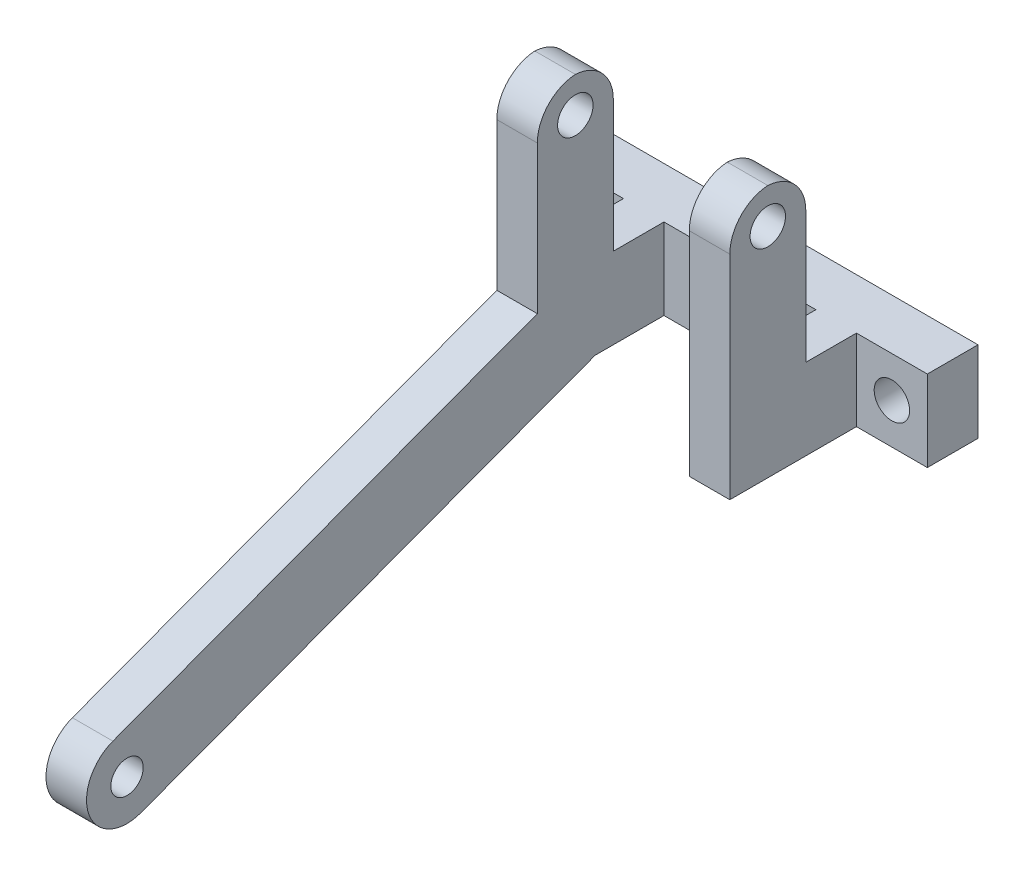
SolidWorks part; units mm, degrees
ref_plane "Front Plane" through (0, 0, 0) normal (0, 0, 1) x (1, 0, 0)
ref_plane "Top Plane" through (0, 0, 0) normal (0, 1, 0) x (1, 0, 0)
ref_plane "Right Plane" through (0, 0, 0) normal (1, 0, 0) x (0, 0, -1)
sketch "Sketch1" plane through (0, 0, 0) normal (0, 0, 1) x (1, 0, 0)
  line L0 (15, 0) -> (-15, 0) construction
  line L1 (-18.5, 4) -> (18.5, 4)
  line L2 (-18.5, 4) -> (-18.5, -4)
  line L3 (-18.5, -4) -> (18.5, -4)
  line L4 (18.5, 4) -> (18.5, -4)
  line L5 (-18.5, 4) -> (18.5, -4) construction
  line L6 (-18.5, -4) -> (18.5, 4) construction
  line L7 (0, -4) -> (0, 4) construction
  circle A0 centre (-15, 0) radius 1.75
  circle A1 centre (15, 0) radius 1.75
  point P0 (0, 0)
  point P12 (0, 0)
  dimension "D3" = 3.5
  dimension "D1" = 37
  dimension "D2" = 8
  dimension "D4" = 15
extrude "Boss-Extrude1" add sketch "Sketch1" along normal blind 5
sketch "Sketch2" plane through (0, 0, 5) normal (0, 0, 1) x (1, 0, 0)
  line L0 (0, 4) -> (0, -4) construction
  line L1 (18.5, 4) -> (-18.5, 4) construction
  line L2 (-18.5, -4) -> (18.5, -4) construction
  line L3 (11.5, -4) -> (7.5, 4) construction
  line L4 (-11.5, 4) -> (-7.5, 4)
  line L5 (-11.5, 4) -> (-11.5, -4)
  line L6 (-11.5, -4) -> (-7.5, -4)
  line L7 (-7.5, 4) -> (-7.5, -4)
  line L8 (-11.5, 4) -> (-7.5, -4) construction
  line L9 (-11.5, -4) -> (-7.5, 4) construction
  line L10 (11.5, 4) -> (7.5, -4) construction
  line L11 (7.5, 4) -> (7.5, -4)
  line L12 (11.5, -4) -> (7.5, -4)
  line L13 (11.5, 4) -> (11.5, -4)
  line L14 (11.5, 4) -> (7.5, 4)
  point P6 (-9.5, 0)
  point P15 (9.5, 0)
  dimension "D1" = 7.5
  dimension "D2" = 4
extrude "Boss-Extrude2" add sketch "Sketch2" along normal blind 12.5
sketch "Sketch4" plane through (0, 4, 0) normal (0, 1, 0) x (1, 0, 0)
  line L0 (-7.5, -17.5) -> (-7.5, -5) construction
  line L1 (-11.5, -17.5) -> (-7.5, -17.5)
  line L2 (-11.5, -17.5) -> (-11.5, -10)
  line L3 (-11.5, -10) -> (-7.5, -10)
  line L4 (-7.5, -17.5) -> (-7.5, -10)
  line L5 (0, 0) -> (0, -5) construction
  line L6 (7.5, -5) -> (-7.5, -5) construction
  line L7 (7.5, -17.5) -> (7.5, -10)
  line L8 (11.5, -10) -> (7.5, -10)
  line L9 (11.5, -17.5) -> (11.5, -10)
  line L10 (11.5, -17.5) -> (7.5, -17.5)
  dimension "D1" = 7.5
extrude "Boss-Extrude3" add sketch "Sketch4" along normal blind 17
sketch "Sketch3" plane through (-11.5, 0, 0) normal (-1, 0, 0) x (0, 0, 1)
  line L0 (10, 17.5) -> (17.5, 17.5) construction
  line L4 (10, 21) -> (10, 4) construction
  line L5 (17.5, 21) -> (17.5, -4) construction
  line L6 (13.75, 17.5) -> (13.75, 21) construction
  line L7 (10, 21) -> (17.5, 21) construction
  circle A0 centre (13.75, 17.5) radius 1.75
  dimension "D1" = 3.5
  dimension "D2" = 17.5
extrude "Cut-Extrude1" cut sketch "Sketch3" against normal through all
fillet "Fillet1" radius 4 4 edges at (-9.5, 21, 10) (9.5, 21, 10) (9.5, 21, 17.5) (-9.5, 21, 17.5)
sketch "Sketch5" plane through (-7.5, 0, 0) normal (1, 0, 0) x (0, 0, -1)
  line L0 (-10, 17) -> (-10, 4) construction
  line L1 (-10, 6.5) -> (-13, 6.5)
  line L2 (-10, 6.5) -> (-10, 1.5)
  line L3 (-10, 1.5) -> (-13, 1.5)
  line L4 (-13, 6.5) -> (-13, 1.5)
  line L5 (-10, 4) -> (-5, 4) construction
  dimension "D1" = 3
  dimension "D2" = 5
  dimension "D3" = 2.5
extrude "Boss-Extrude4" [suppressed] add sketch "Sketch5" along normal up to next
sketch "Sketch6" plane through (-11.5, 0, 0) normal (-1, 0, 0) x (0, 0, 1)
  line L0 (56.6083, -20.6814) -> (11.7824, -4)
  line L1 (17.5, -4) -> (5, -4) construction
  line L2 (11.7824, -4) -> (17.5, 2.4083)
  line L3 (13.75, 17.5) -> (58.0033, -16.9326) construction
  line L4 (17.5, 2.4083) -> (59.3984, -13.1837)
  line L5 (59.3984, -13.1837) -> (56.6083, -20.6814) construction
  line L6 (13.75, 17.5) -> (13.75, -4) construction
  line L7 (17.5, 17) -> (17.5, -4) construction
  circle A0 centre (58.0033, -16.9326) radius 1.6
  arc A1 (56.6083, -20.6814) -> (59.3984, -13.1837) centre (58.0033, -16.9326) ccw
  dimension "D1" = 3.2
  dimension "D2" = 8
  dimension "D3" = 52.114
  dimension "D4" = 56.071
  dimension "D5" = 1.9676
extrude "Boss-Extrude5" add sketch "Sketch6" against normal up to surface (4 mm away) up to face at (-7.5, 15.75, 13.75)
equation "\"X-ROD-SPACING\"=45"
equation "\"Y-ROD-SPACING\"=75"
equation "\"Z-ROD-SPACING\"=17.5"
equation "\"Y-BED-OFFSET\"=2"
equation "\"Y-BED-ROD-INSET\"=3.5"
equation "\"Y-BED-SCREW-SPACING\"=209"
equation "\"Y-BED-SCREW-CUTOUT-SLOT-HEIGHT\"=2"
equation "\"T-SLOT-NUT-FILLET-RADIUS\"=0.25"
equation "\"T-SLOT-SCREW-SHAFT-RADIUS\"=1.75"
equation "\"T-SLOT-SCREW-SHAFT-CUTOUT-LENGTH\"=10.5"
equation "\"T-SLOT-NUT-DEPTH\"=4.2"
equation "\"T-SLOT-NUT-WIDTH\"=3"
equation "\"T-SLOT-NUT-END-DISTANCE\"=8"
equation "\"ACRYLIC-THICKNESS\"=10"
equation "\"ACRYLIC-THICKNESS2\"=4.5"
equation "\"ACRYLIC-TAB-CUTOUT-SIZE\"=\"ACRYLIC-THICKNESS\"+\"ACRYLIC-TAB-TOLERANCE\"*2"
equation "\"ACRYLIC-TAB-TOLERANCE\"=.1"
equation "\"ACRYLIC-TAB-WIDTH\"=\"ACRYLIC-THICKNESS\""
equation "\"ACRYLIC-M3-HOLE\"=3.1"
equation "\"SMOOTHROD-CAP-SCREW-DISTANCE\"=20"
equation "\"FRAME-WIDTH-INNER\"=370"
equation "\"NEMA17-HOLE-SPACING\"=31"
equation "\"NEMA17-CENTRAL-CUTOUT\"=22.5"
equation "\"Z-BRACKET-REACH\"=55"
equation "\"Z-ROD-INSET\"=16"
equation "\"TOP-BRACKET-SPACING\"=40"
equation "\"SMOOTHROD-X-LENGTH\"=350"
equation "\"SMOOTHROD-Y-LENGTH\"=350"
equation "\"SMOOTHROD-Z-LENGTH\"=350"
equation "\"SMOOTHROD-TIGHTENING-HEADROOM\"=.25"
equation "\"LEADSCREW-Z-LENGTH\"=300"
equation "\"SCREW-LENGTH-FRAME\"=\"ACRYLIC-THICKNESS\" + 10"
equation "\"SCREW-LENGTH-MOTOR\"=\"ACRYLIC-THICKNESS\" + 5"
equation "\"SCREW-LENGTH-EXTRUDER\"=28"
equation "\"SCREW-HEAD-RADIUS\"=6"
equation "\"PRINTED-X-SMOOTHROD-DIAMETER\"=8.2"
equation "\"PRINTED-X-SMOOTHROD-CUTOUT\"=10"
equation "\"PRINTED-X-BASE-HEIGHT\"=10"
equation "\"PRINTED-LM8UU-CUTOUT-SIZE\"=15.25"
equation "\"PRINTED-LM8UU-CUTOUT-LENGTH\"=24.5"
equation "\"PRINTED-X-IDLER-HEIGHT\"=16"
equation "\"PSU-MOUNTING-WIDTH\"=95"
equation "\"PSU-MOUNTING-HEIGHT\"=177"
equation "\"Y-BELT-TO-ROD-DISTANCE\"=20"
equation "\"SPOOL-HOLDER-ROD-SPACING\"=150"
equation "\"ACRYLIC-X-CARRIAGE-WIDTH\"=55"
equation "\"ACRYLIC-X-CARRIAGE-HEIGHT\"=75"
equation "\"ACRYLIC-X-CARRIAGE-LM8UU-CUTOUT-WIDTH\"=24.25"
equation "\"ACRYLIC-X-CARRIAGE-LM8UU-CUTOUT-HEIGHT\"=11.5"
equation "\"ACRYLIC-X-CARRIAGE-SCREW-SPACING-X\"=15"
equation "\"ACRYLIC-X-CARRIAGE-SCREW-SPACING-Y\"=33"
equation "\"ACRYLIC-X-CARRIAGE-CENTER-TAB-SPACING\"=14"
equation "\"ACRYLIC-X-CARRIAGE-EXTRUDER-OFFSET\"=26"
equation "\"ACRYLIC-X-CARRIAGE-EXTRUDER-ANGLE\"=90"
equation "\"ACRYLIC-X-CARRIAGE-EXTRUDER-SHELF-DEPTH\"=\"ACRYLIC-X-CARRIAGE-EXTRUDER-OFFSET\" + 28"
equation "\"ACRYLIC-X-CARRIAGE-EXTRUDER-BRACE-SPACING\"=23"
equation "\"ACRYLIC-X-CARRIAGE-EXTRUDER-BRACE-TAB-OFFSET\"=20"
equation "\"ACRYLIC-X-CARRIAGE-EXTRUDER-BRACE-HEIGHT\"=35"
equation "\"ACRYLIC-X-CARRIAGE-EXTRUDER-BRACE-SCREW-SPACING\"=22"
equation "\"ACRYLIC-X-CARRIAGE-DUAL-WIDTH-MULTIPLIER\"=1.65"
equation "\"ACRYLIC-X-CARRIAGE-DUAL-HOTEND-SPACING\"=42"
equation "\"ACRYLIC-X-CARRIAGE-DUAL-WIDTH\"=103"
equation "\"ACRYLIC-X-CARRIAGE-DUAL-HOTEND-SEPARATION\"=35"
equation "\"ACRYLIC-X-CARRIAGE-DUAL-MOUNT-PLATE-DEPTH\"=76"
equation "\"ACRYLIC-X-CARRIAGE-DUAL-MOUNT-BRACE-WIDTH\"=45"
equation "\"ACRYLIC-X-CARRIAGE-DUAL-MOUNT-SCREW-WIDTH\"=40"
equation "\"D3@Sketch1\"=3.5"
equation "\"PRINTED-M3-HOLE\"=3.5"
equation "\"BLOWER-FAN-WIDTH\"=15"
equation "\"D1@Sketch2\"=\"BLOWER-FAN-WIDTH\"/2"
